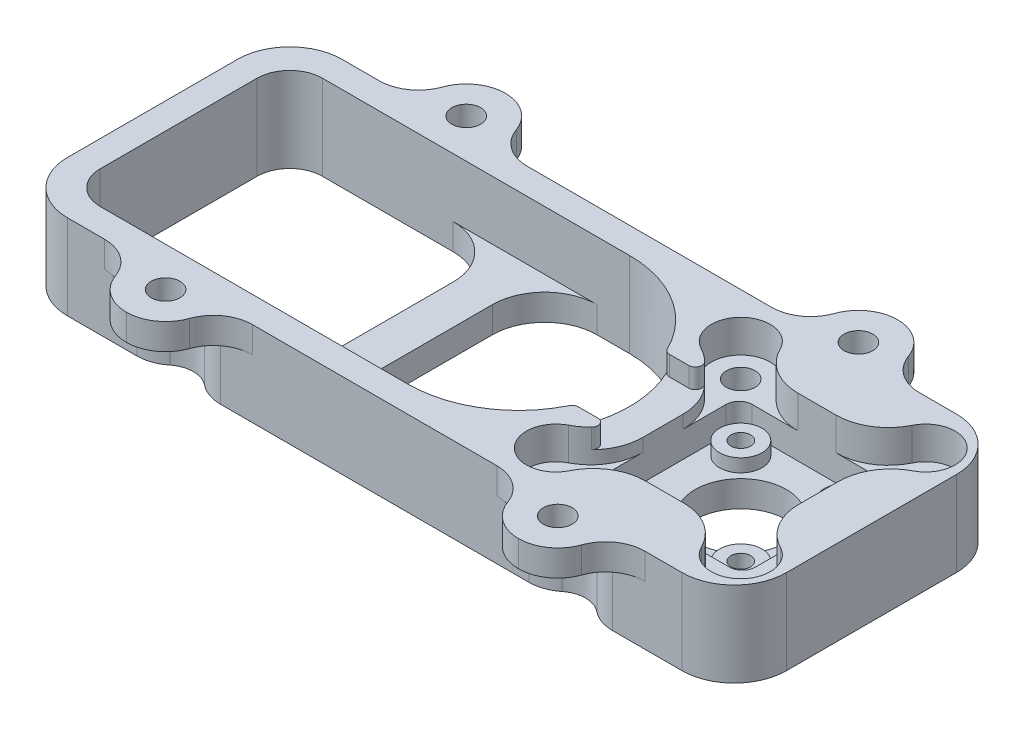
SolidWorks part; units mm, degrees
ref_plane "Plan de face" through (0, 0, 0) normal (0, 0, 1) x (1, 0, 0)
ref_plane "Plan de dessus" through (0, 0, 0) normal (0, 1, 0) x (1, 0, 0)
ref_plane "Plan de droite" through (0, 0, 0) normal (1, 0, 0) x (0, 0, -1)
sketch "Esquisse1" plane through (0, 0, 0) normal (0, 1, 0) x (1, 0, 0)
  line L0 (0, 20) -> (0, 0) construction
  line L1 (0, 0) -> (14.1421, 14.1421) construction
  line L2 (-30, 0) -> (30, 0) construction
  line L3 (8, 8) -> (-8, 8) construction
  line L4 (8, 8) -> (8, -8) construction
  line L5 (8, -8) -> (-8, -8) construction
  line L6 (-8, 8) -> (-8, -8) construction
  line L7 (8, 8) -> (-8, -8) construction
  line L8 (8, -8) -> (-8, 8) construction
  line L9 (-90, 21) -> (30, 21)
  line L10 (-90, 21) -> (-90, -21)
  line L11 (-90, -21) -> (30, -21)
  line L12 (30, 21) -> (30, -21)
  line L13 (-90, 21) -> (30, -21) construction
  line L14 (-90, -21) -> (30, 21) construction
  circle A0 centre (0, 0) radius 20 construction
  circle A1 centre (14.1421, 14.1421) radius 2.2
  circle A2 centre (14.1421, -14.1421) radius 2.2
  circle A3 centre (-14.1421, -14.1421) radius 2.2
  circle A4 centre (-14.1421, 14.1421) radius 2.2
  circle A5 centre (-8, 8) radius 1.5
  circle A6 centre (-8, -8) radius 1.5
  circle A7 centre (8, -8) radius 1.5
  circle A8 centre (8, 8) radius 1.5
  point P15 (0, 0)
  point P25 (-30, 0)
  point P26 (19.9701, -21.8687)
  point P29 (30, 21)
  dimension "D1" = 40
  dimension "D2" = 45
  dimension "D4" = 4.4
  dimension "D5" = 3
  dimension "D6" = 16
  dimension "D7" = 16
  dimension "D8" = 42
  dimension "D9" = 120
  dimension "D3" = 4
extrude "Boss.-Extru.1" add sketch "Esquisse1" along normal blind 8
sketch "Esquisse2" plane through (0, 8, 0) normal (0, 1, 0) x (1, 0, 0)
  line L1 (11.9, 11.65) -> (-11.9, 11.65)
  line L2 (11.9, 11.65) -> (11.9, -11.65)
  line L3 (11.9, -11.65) -> (-11.9, -11.65)
  line L4 (-11.9, 11.65) -> (-11.9, -11.65)
  line L5 (11.9, 11.65) -> (-11.9, -11.65) construction
  line L6 (11.9, -11.65) -> (-11.9, 11.65) construction
  point P0 (0, 0)
  dimension "D1" = 23.3
  dimension "D2" = 23.8
extrude "Enlèv. mat.-Extru.1" cut sketch "Esquisse2" against normal blind 2
fillet "Congé1" radius 2 4 edges at (-11.9, 7, 11.65) (11.9, 7, 11.65) (11.9, 7, -11.65) (-11.9, 7, -11.65)
sketch "Esquisse4" plane through (0, 6, 0) normal (0, 1, 0) x (1, 0, 0)
  line L4 (-11.9, 9.65) -> (-11.9, -9.65)
  line L5 (-9.9, -11.65) -> (9.9, -11.65)
  line L6 (11.9, -9.65) -> (11.9, 9.65)
  line L7 (9.9, 11.65) -> (-9.9, 11.65)
  line L8 (-11.9, 9.65) -> (-11.9, -9.65)
  line L9 (-9.9, -11.65) -> (9.9, -11.65)
  line L10 (11.9, -9.65) -> (11.9, 9.65)
  line L11 (9.9, 11.65) -> (-9.9, 11.65)
  circle A0 centre (8, 8) radius 3.25
  circle A1 centre (-8, 8) radius 3.25
  circle A2 centre (-8, -8) radius 3.25
  circle A3 centre (8, -8) radius 3.25
  arc A4 (-11.9, -9.65) -> (-9.9, -11.65) centre (-9.9, -9.65) ccw
  arc A5 (9.9, -11.65) -> (11.9, -9.65) centre (9.9, -9.65) ccw
  arc A6 (11.9, 9.65) -> (9.9, 11.65) centre (9.9, 9.65) ccw
  arc A7 (-9.9, 11.65) -> (-11.9, 9.65) centre (-9.9, 9.65) ccw
  arc A8 (-11.9, -9.65) -> (-9.9, -11.65) centre (-9.9, -9.65) ccw
  arc A9 (9.9, -11.65) -> (11.9, -9.65) centre (9.9, -9.65) ccw
  arc A10 (11.9, 9.65) -> (9.9, 11.65) centre (9.9, 9.65) ccw
  arc A11 (-9.9, 11.65) -> (-11.9, 9.65) centre (-9.9, 9.65) ccw
  dimension "D2" = 6.5
  dimension "D1" = 0
extrude "Enlèv. mat.-Extru.2" cut sketch "Esquisse4" against normal blind 2
sketch "Esquisse5" plane through (0, 4, 0) normal (0, 1, 0) x (1, 0, 0)
  circle A0 centre (0, 0) radius 7
  dimension "D1" = 14
extrude "Enlèv. mat.-Extru.3" cut sketch "Esquisse5" against normal through all
sketch "Esquisse6" plane through (0, 8, 0) normal (0, 1, 0) x (1, 0, 0)
  line L0 (-68, 0) -> (-34, 0) construction
  line L1 (-68, 17) -> (-34, 17)
  line L2 (-68, -17) -> (-34, -17)
  line L3 (30, 21) -> (-90, 21) construction
  line L4 (-90, 21) -> (-90, -21) construction
  arc A0 (-68, 17) -> (-68, -17) centre (-68, 0) ccw
  arc A1 (-34, -17) -> (-34, 17) centre (-34, 0) ccw
  point P2 (-51, 0)
  dimension "D1" = 4
  dimension "D2" = 34
  dimension "D3" = 22
extrude "Enlèv. mat.-Extru.4" cut sketch "Esquisse6" against normal through all
sketch "Esquisse8" plane through (0, 8, 0) normal (0, 1, 0) x (1, 0, 0)
  line L0 (-34, 17) -> (-68, 17) construction
  line L1 (-53, 17) -> (-47, 17)
  line L2 (-53, 17) -> (-53, -17)
  line L3 (-53, -17) -> (-47, -17)
  line L4 (-47, 17) -> (-47, -17)
  line L5 (-53, 17) -> (-47, -17) construction
  line L6 (-53, -17) -> (-47, 17) construction
  line L7 (-68, -17) -> (-34, -17) construction
  line L8 (-90, 21) -> (-90, -21) construction
  point P4 (-50, 0)
  dimension "D1" = 6
  dimension "D2" = 40
extrude "Boss.-Extru.2" add sketch "Esquisse8" against normal blind 8
fillet "Congé2" radius 8 4 edges at (-47, 4, -17) (-47, 4, 17) (-53, 4, 17) (-53, 4, -17)
sketch "Esquisse9" plane through (0, 8, 0) normal (0, 1, 0) x (1, 0, 0)
  line L0 (-90, -21) -> (30, -21) construction
  line L1 (30, 21) -> (20, 21)
  line L2 (30, 21) -> (30, -21)
  line L3 (30, -21) -> (20, -21)
  line L4 (20, 21) -> (20, -21)
  line L5 (30, 21) -> (20, -21) construction
  line L6 (30, -21) -> (20, 21) construction
  point P4 (25, 0)
  dimension "D1" = 20
extrude "Enlèv. mat.-Extru.5" cut sketch "Esquisse9" against normal through all
fillet "Congé3" radius 8 4 edges at (-90, 4, -21) (-90, 4, 21) (20, 4, 21) (20, 4, -21)
sketch "Esquisse10" plane through (0, 8, 0) normal (0, 1, 0) x (1, 0, 0)
  line L4 (12, 21) -> (-82, 21)
  line L5 (-90, 13) -> (-90, -13)
  line L6 (-82, -21) -> (12, -21)
  line L7 (20, -13) -> (20, 13)
  line L8 (12, 21) -> (-82, 21)
  line L9 (-90, 13) -> (-90, -13)
  line L10 (-82, -21) -> (12, -21)
  line L11 (20, -13) -> (20, 13)
  line L12 (-39, -17) -> (-34, -17)
  line L13 (-47, 9) -> (-47, -9)
  line L14 (-34, 17) -> (-39, 17)
  line L15 (-39, -17) -> (-34, -17)
  line L16 (-47, 9) -> (-47, -9)
  line L17 (-34, 17) -> (-39, 17)
  line L19 (-61, 17) -> (-68, 17)
  line L20 (-53, -9) -> (-53, 9)
  line L21 (-68, -17) -> (-61, -17)
  line L22 (-61, 17) -> (-68, 17)
  line L23 (-53, -9) -> (-53, 9)
  line L24 (-68, -17) -> (-61, -17)
  line L27 (-11.9, 9.65) -> (-11.9, -9.65)
  line L28 (9.9, 11.65) -> (-9.9, 11.65)
  line L29 (11.9, -9.65) -> (11.9, 9.65)
  line L30 (-9.9, -11.65) -> (9.9, -11.65)
  line L31 (-11.9, 9.65) -> (-11.9, -9.65)
  line L32 (9.9, 11.65) -> (-9.9, 11.65)
  line L33 (11.9, -9.65) -> (11.9, 9.65)
  line L34 (-9.9, -11.65) -> (9.9, -11.65)
  arc A0 (-10.4471, 11.5737) -> (-11.7893, 10.3063) centre (-14.1421, 14.1421) ccw
  arc A1 (11.7893, 10.3063) -> (10.4471, 11.5737) centre (14.1421, 14.1421) ccw
  arc A2 (-11.7893, -10.3063) -> (-10.4471, -11.5737) centre (-14.1421, -14.1421) ccw
  arc A3 (10.4471, -11.5737) -> (11.7893, -10.3063) centre (14.1421, -14.1421) ccw
  arc A4 (-82, 21) -> (-90, 13) centre (-82, 13) ccw
  arc A5 (-90, -13) -> (-82, -21) centre (-82, -13) ccw
  arc A6 (12, -21) -> (20, -13) centre (12, -13) ccw
  arc A7 (20, 13) -> (12, 21) centre (12, 13) ccw
  arc A8 (-82, 21) -> (-90, 13) centre (-82, 13) ccw
  arc A9 (-90, -13) -> (-82, -21) centre (-82, -13) ccw
  arc A10 (12, -21) -> (20, -13) centre (12, -13) ccw
  arc A11 (20, 13) -> (12, 21) centre (12, 13) ccw
  arc A12 (-11.7893, 10.3063) -> (-11.9, 9.65) centre (-9.9, 9.65) ccw
  arc A13 (10.4471, 11.5737) -> (9.9, 11.65) centre (9.9, 9.65) ccw
  arc A14 (11.7893, -10.3063) -> (11.9, -9.65) centre (9.9, -9.65) ccw
  arc A15 (-47, -9) -> (-39, -17) centre (-39, -9) ccw
  arc A16 (-39, 17) -> (-47, 9) centre (-39, 9) ccw
  arc A17 (-34, -17) -> (-34, 17) centre (-34, 0) ccw
  arc A18 (-47, -9) -> (-39, -17) centre (-39, -9) ccw
  arc A19 (-39, 17) -> (-47, 9) centre (-39, 9) ccw
  arc A20 (-34, -17) -> (-34, 17) centre (-34, 0) ccw
  arc A21 (-53, 9) -> (-61, 17) centre (-61, 9) ccw
  arc A22 (-61, -17) -> (-53, -9) centre (-61, -9) ccw
  arc A23 (-68, 17) -> (-68, -17) centre (-68, 0) ccw
  arc A24 (-53, 9) -> (-61, 17) centre (-61, 9) ccw
  arc A25 (-61, -17) -> (-53, -9) centre (-61, -9) ccw
  arc A26 (-68, 17) -> (-68, -17) centre (-68, 0) ccw
  arc A27 (-10.4471, -11.5737) -> (-9.9, -11.65) centre (-9.9, -9.65) ccw
  arc A28 (-9.9, 11.65) -> (-11.9, 9.65) centre (-9.9, 9.65) ccw
  arc A29 (11.9, 9.65) -> (9.9, 11.65) centre (9.9, 9.65) ccw
  arc A30 (9.9, -11.65) -> (11.9, -9.65) centre (9.9, -9.65) ccw
  arc A31 (-11.9, -9.65) -> (-9.9, -11.65) centre (-9.9, -9.65) ccw
  arc A32 (-9.9, 11.65) -> (-10.4471, 11.5737) centre (-9.9, 9.65) ccw
  arc A33 (11.9, 9.65) -> (11.7893, 10.3063) centre (9.9, 9.65) ccw
  arc A34 (9.9, -11.65) -> (10.4471, -11.5737) centre (9.9, -9.65) ccw
  arc A35 (-11.9, -9.65) -> (-11.7893, -10.3063) centre (-9.9, -9.65) ccw
  dimension "D4" = 9
  dimension "D1" = 0
  dimension "D2" = 0
  dimension "D3" = 0
  dimension "D5" = 0
extrude "Boss.-Extru.3" add sketch "Esquisse10" along normal blind 5
fillet "Congé4" radius 8 8 edges at (-10.4471, 10.5, 11.5737) (-11.7893, 10.5, 10.3063) (10.4471, 10.5, 11.5737) (11.7893, 10.5, 10.3063) (11.7893, 10.5, -10.3063) (10.4471, 10.5, -11.5737) (-11.7893, 10.5, -10.3063) (-10.4471, 10.5, -11.5737)
sketch "Esquisse11" plane through (0, 13, 0) normal (0, 1, 0) x (1, 0, 0)
  line L0 (-68, 0) -> (-34, 0) construction
  line L1 (-68, 17) -> (-34, 17)
  line L2 (-68, -17) -> (-34, -17)
  arc A0 (-68, 17) -> (-68, -17) centre (-68, 0) ccw
  arc A1 (-34, -17) -> (-34, 17) centre (-34, 0) ccw
  arc A2 (-34, -17) -> (-34, 17) centre (-34, 0) ccw construction
  arc A3 (-68, 17) -> (-68, -17) centre (-68, 0) ccw construction
  point P2 (-51, 0)
extrude "Enlèv. mat.-Extru.6" cut sketch "Esquisse11" against normal blind 9
sketch "Esquisse12" plane through (0, 13, 0) normal (0, 1, 0) x (1, 0, 0)
  line L0 (0, 0) -> (-36, 0) construction
  line L1 (-38, 5) -> (-34, 5)
  line L2 (-38, 5) -> (-38, -5)
  line L3 (-38, -5) -> (-34, -5)
  line L4 (-34, 5) -> (-34, -5)
  line L5 (-38, 5) -> (-34, -5) construction
  line L6 (-38, -5) -> (-34, 5) construction
  circle A0 centre (0, 0) radius 46 construction
  point P6 (-36, 0)
  dimension "D1" = 92
  dimension "D2" = 36
  dimension "D3" = 10
  dimension "D4" = 4
sketch "Esquisse13" plane through (0, 13, 0) normal (0, 1, 0) x (1, 0, 0)
  line L0 (-34, 17) -> (-68, 17) construction
  line L1 (-62.6043, 17) -> (-86, 17)
  line L2 (-62.6043, 17) -> (-62.6043, -17)
  line L3 (-62.6043, -17) -> (-86, -17)
  line L4 (-86, 17) -> (-86, -17)
  line L5 (-62.6043, 17) -> (-86, -17) construction
  line L6 (-62.6043, -17) -> (-86, 17) construction
  line L7 (-68, -17) -> (-34, -17) construction
  line L8 (-90, 13) -> (-90, -13) construction
  point P4 (-74.3021, 0)
  point P7 (0, 0)
  dimension "D1" = 4
extrude "Enlèv. mat.-Extru.7" cut sketch "Esquisse13" against normal through all
fillet "Congé5" radius 5 2 edges at (-86, 6.5, 17) (-86, 6.5, -17)
sketch "Esquisse14" plane through (0, 0, -21) normal (0, 0, -1) x (-1, 0, 0)
  line L0 (35, 0) -> (35, 13) construction
  line L1 (-12, 0) -> (82, 0) construction
  line L2 (-12, 13) -> (82, 13) construction
  line L3 (-1, 13) -> (11, 9) construction
  line L4 (71, 9) -> (59, 9)
  line L5 (71, 9) -> (71, 13)
  line L6 (71, 13) -> (59, 13)
  line L7 (59, 9) -> (59, 13)
  line L8 (71, 9) -> (59, 13) construction
  line L9 (71, 13) -> (59, 9) construction
  line L10 (-1, 9) -> (11, 13) construction
  line L11 (11, 9) -> (11, 13)
  line L12 (-1, 13) -> (11, 13)
  line L13 (-1, 9) -> (-1, 13)
  line L14 (-1, 9) -> (11, 9)
  point P10 (65, 11)
  point P15 (5, 11)
  point P16 (0, 0)
  point P17 (0, 0)
  point P18 (71, 0)
  point P19 (0, 0)
  point P20 (59, 13)
  dimension "D1" = 12
  dimension "D2" = 4
  dimension "D3" = 60
extrude "Boss.-Extru.4" add sketch "Esquisse14" along normal blind 8
sketch "Esquisse15" plane through (0, 0, 21) normal (0, 0, 1) x (1, 0, 0)
  line L4 (-11, 13) -> (-11, 9)
  line L5 (1, 13) -> (-11, 13)
  line L6 (1, 9) -> (1, 13)
  line L7 (-11, 9) -> (1, 9)
  line L8 (-11, 13) -> (-11, 9)
  line L9 (1, 13) -> (-11, 13)
  line L10 (1, 9) -> (1, 13)
  line L11 (-11, 9) -> (1, 9)
  line L12 (-71, 9) -> (-59, 9)
  line L13 (-59, 9) -> (-59, 13)
  line L14 (-59, 13) -> (-71, 13)
  line L15 (-71, 13) -> (-71, 9)
  line L16 (-71, 9) -> (-59, 9)
  line L17 (-59, 9) -> (-59, 13)
  line L18 (-59, 13) -> (-71, 13)
  line L19 (-71, 13) -> (-71, 9)
  dimension "D1" = 0
  dimension "D2" = 0
extrude "Boss.-Extru.5" add sketch "Esquisse15" along normal blind 8
fillet "Congé6" radius 6 8 edges at (-71, 11, -29) (-59, 11, -29) (-11, 11, -29) (1, 11, -29) (1, 11, 29) (-11, 11, 29) (-59, 11, 29) (-71, 11, 29)
sketch "Esquisse16" plane through (0, 13, 0) normal (0, 1, 0) x (1, 0, 0)
  line L0 (6.5, 21) -> (6.5, 0) construction
  line L1 (12, 21) -> (1, 21) construction
  line L2 (0, 0) -> (-36, 0) construction
  line L3 (6.5, 0) -> (0, 0) construction
  line L4 (-35, 21) -> (-35, -27.8111) construction
  line L5 (-11, 21) -> (-59, 21) construction
  circle A0 centre (-65, 23) radius 2.2
  circle A1 centre (-5, -23) radius 2.2
  circle A2 centre (-5, 23) radius 2.2
  circle A3 centre (-65, -23) radius 2.2
  dimension "D1" = 4.4
extrude "Enlèv. mat.-Extru.8" cut sketch "Esquisse16" against normal through all
sketch "Esquisse17" plane through (0, 0, 0) normal (0, 1, 0) x (1, 0, 0)
  circle A0 centre (-65, 23) radius 4.25
  circle A1 centre (-5, 23) radius 4.25
  circle A2 centre (-65, -23) radius 4.25
  circle A3 centre (-5, -23) radius 4.25
  point P12 (-5.0653, -23.8243)
  point P13 (-5, -23)
  point P15 (-5, 23.8243)
  point P16 (-5, 23)
  dimension "D1" = 8.5
extrude "Enlèv. mat.-Extru.9" cut sketch "Esquisse17" along normal blind 9
fillet "Congé7" radius 6 8 edges at (-68.75, 4.5, 21) (-61.25, 4.5, 21) (-8.75, 4.5, 21) (-1.25, 4.5, 21) (-1.25, 4.5, -21) (-8.75, 4.5, -21) (-61.25, 4.5, -21) (-68.75, 4.5, -21)
fillet "Congé8" radius 6 8 edges at (-11, 11, 20.9861) (1, 11, 20.9861) (-59, 11, 20.9861) (-71, 11, 20.9861) (-71, 11, -20.9861) (-59, 11, -20.9861) (-11, 11, -20.9861) (1, 11, -20.9861)
sketch "Esquisse19" plane through (0, 13, 0) normal (0, 1, 0) x (1, 0, 0)
  line L1 (-5.967, 6.9619) -> (-23.4359, 6.9619)
  line L2 (-5.967, 6.9619) -> (-5.967, -6.9619)
  line L3 (-5.967, -6.9619) -> (-23.4359, -6.9619)
  line L4 (-23.4359, 6.9619) -> (-23.4359, -6.9619)
  line L5 (-5.967, 6.9619) -> (-23.4359, -6.9619) construction
  line L6 (-5.967, -6.9619) -> (-23.4359, 6.9619) construction
  point P0 (-14.7014, 0)
extrude "Enlèv. mat.-Extru.10" cut sketch "Esquisse19" against normal blind 3
fillet "Congé9" radius 1 4 edges at (-12.9232, 11.5, -6.9619) (-18.4909, 11.5, -6.9619) (-12.9232, 11.5, 6.9619) (-18.4909, 11.5, 6.9619)
